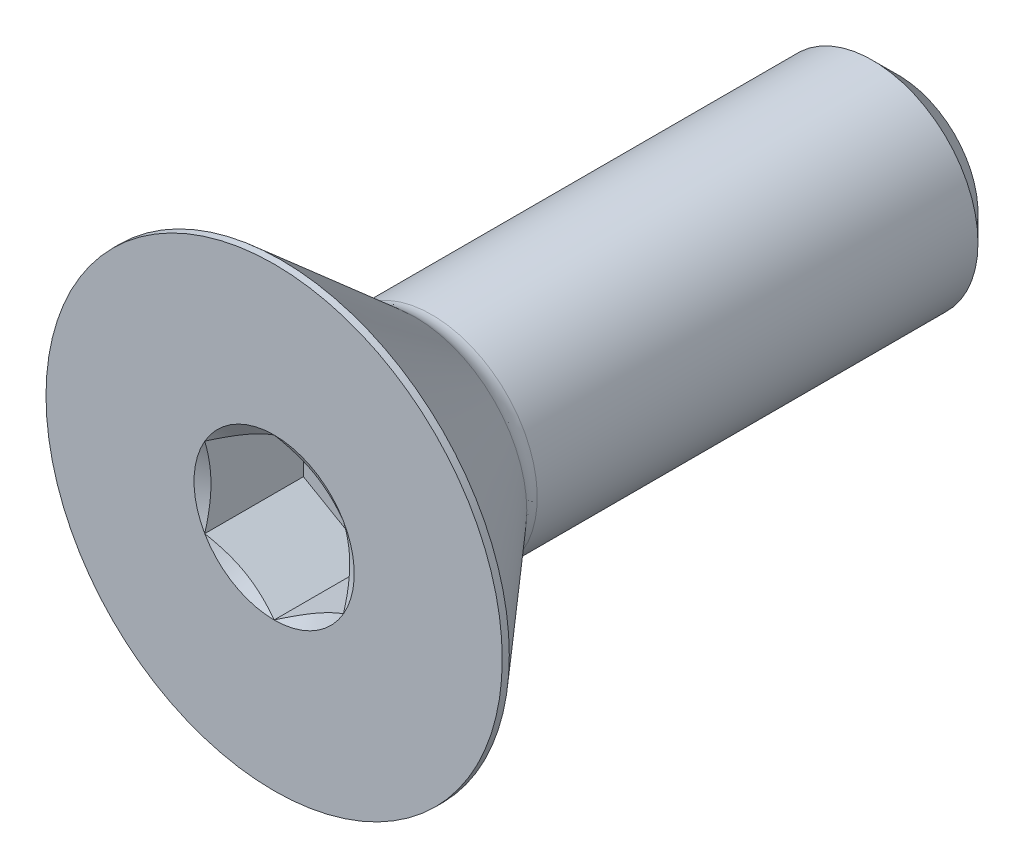
SolidWorks part; units mm, degrees
material "Plain Carbon Steel"
ref_plane "Front" through (0, 0, 0) normal (0, 0, 1) x (1, 0, 0)
ref_plane "Top" through (0, 0, 0) normal (0, 1, 0) x (1, 0, 0)
ref_plane "Right" through (0, 0, 0) normal (1, 0, 0) x (0, 0, -1)
sketch "Sketch1" plane through (0, 0, 0) normal (1, 0, 0) x (0, 0, -1)
  line L0 (0, 5.2197) -> (0.1613, 5.2197) construction
  line L1 (0.1613, 5.2197) -> (3.2258, 2.5558) construction
  line L2 (0, 2.413) -> (14.2875, 2.413)
  line L3 (14.2875, 2.413) -> (14.2875, 0)
  line L4 (14.2875, 0) -> (0, 0)
  line L5 (0, 0) -> (0, 5.2197) construction
  line L6 (0, 5.2197) -> (0, -5.2197) construction
  line L7 (14.2875, 2.413) -> (14.2875, -2.413) construction
  line L8 (0, -5.2197) -> (0.1613, -5.2197) construction
  line L9 (0.1613, -5.2197) -> (3.2258, -2.5558) construction
  line L11 (0, 2.413) -> (0, 0)
  line L12 (3.6076, 2.413) -> (3.6076, 0) construction
  line L13 (-11.1125, 0) -> (-11.1125, 2.413) construction
  arc A1 (3.2258, 2.5558) -> (3.6076, 2.413) centre (3.6076, 2.995) ccw construction
  dimension "D1" = 0.1613
  dimension "Min Thread" = 25.4
revolve "Revolve1" add sketch "Sketch1" angle 360 mid plane about L4
ref_plane "Plane2" through (0, 0, 11.1125) normal (0, 0, 1) x (1, 0, 0)
chamfer "Chamfer1" distance 0.5953 angle 45 1 edges at (-2.413, 0, -14.2875)
sketch "Sketch7" plane through (0, 0, 0) normal (1, 0, 0) x (0, 0, -1)
  line L0 (0, 5.2197) -> (0.1613, 5.2197) construction
  line L1 (0.1613, 5.2197) -> (3.2258, 2.5558) construction
  line L2 (0, 5.2197) -> (0.1613, 5.2197)
  line L3 (0.1613, 5.2197) -> (3.2258, 2.5558)
  line L4 (3.6076, 2.413) -> (3.6076, 0) construction
  line L5 (3.6076, 2.413) -> (3.6076, 0)
  line L7 (0, 0) -> (0, 5.2197) construction
  line L8 (0, 0) -> (0, 5.2197)
  line L9 (0, 0) -> (3.6076, 0)
  line L10 (5.7417, 0) -> (-5.7417, 0) construction
  arc A0 (3.2258, 2.5558) -> (3.6076, 2.413) centre (3.6076, 2.995) ccw construction
  arc A1 (3.2258, 2.5558) -> (3.6076, 2.413) centre (3.6076, 2.995) ccw
revolve "Revolve2" add sketch "Sketch7" angle 360 mid plane about L9
ref_plane "Plane1" through (0, 0, -3.6076) normal (0, 0, 1) x (1, 0, 0)
sketch "Sketch5" plane through (0, 0, 0) normal (0, 0, 1) x (1, 0, 0)
  line L0 (0, 0) -> (-1.8331, 0) construction
  line L1 (0, 0) -> (-2.7496, 1.5875) construction
  line L2 (0, 0) -> (-2.7496, -1.5875) construction
  line L6 (0, 1.8331) -> (0, 1.5119) construction
  line L7 (0, 1.5119) -> (0, 1.1906) construction
  line L9 (0, 1.8331) -> (-1.5875, 0.9165)
  line L10 (-1.5875, 0.9165) -> (-1.5875, -0.9165)
  line L11 (-1.5875, -0.9165) -> (0, -1.8331)
  line L12 (0, -1.8331) -> (1.5875, -0.9165)
  line L13 (1.5875, -0.9165) -> (1.5875, 0.9165)
  line L14 (1.5875, 0.9165) -> (0, 1.8331)
  circle A0 centre (0, 0) radius 1.8331 construction
  circle A1 centre (0, 0) radius 1.5119 construction
  circle A2 centre (0, 0) radius 1.1906 construction
  circle A3 centre (0, 0) radius 1.5875 construction
  dimension "D3" = 2.3813
  dimension "D4" = 30
  dimension "D5" = 30
extrude "Cut-Extrude2" cut sketch "Sketch5" against normal blind 2.2581
sketch "Sketch6" plane through (0, 0, 0) normal (0, 0, 1) x (1, 0, 0)
  circle A0 centre (0, 0) radius 1.8331
extrude "Cut-Extrude3" cut sketch "Sketch6" against normal blind 2.2581 draft 60
sketch "Sketch9" [suppressed] plane through (0, 0, -3.6076) normal (0, 0, 1) x (1, 0, 0)
  circle A1 centre (0, 0) radius 2.413
  circle A2 centre (0, 0) radius 2.413
  point P0 (0, 2.413)
  dimension "D1" = 0
extrude "Boss-Extrude2" [suppressed] add sketch "Sketch9" against normal up to surface (15.4424 mm away) up to plane "Plane2"
move or copy body "Body-Move/Copy1" [suppressed] bodies to move or copy 113
equation "\"D1@Cut-Extrude2\" = \"Head Ht@Sketch1\" * .7"
equation "\"D1@Sketch1\" = \"Head Ht@Sketch1\" * .05"
equation "\"D1@Cut-Extrude3\" = \"D1@Cut-Extrude2\""
equation "\"D3@Sketch5\" = \"Hex@Sketch5\" * .75"
